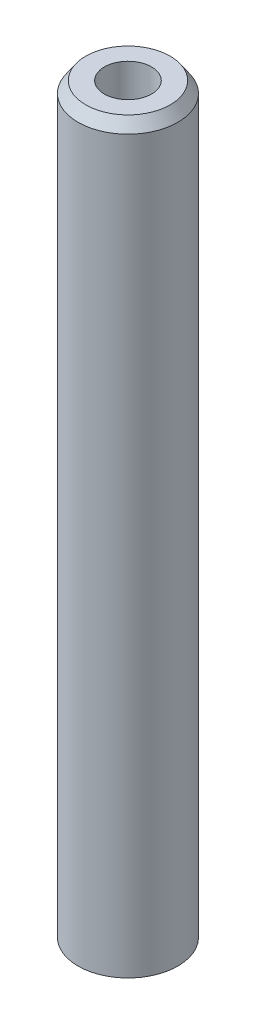
SolidWorks part; units mm, degrees
ref_plane "Front Plane" through (0, 0, 0) normal (0, 0, 1) x (1, 0, 0)
ref_plane "Top Plane" through (0, 0, 0) normal (0, 1, 0) x (1, 0, 0)
ref_plane "Right Plane" through (0, 0, 0) normal (1, 0, 0) x (0, 0, -1)
sketch "Sketch1" plane through (0, 0, 0) normal (0, 1, 0) x (1, 0, 0)
  circle A0 centre (0, 0) radius 10
  dimension "SHAFT_OD" = 20
extrude "Boss-Extrude1" add sketch "Sketch1" along normal blind 150.1847
sketch "Sketch2" plane through (0, 0, 0) normal (0, 1, 0) x (1, 0, 0)
  circle A0 centre (0, 0) radius 4.7216
  dimension "BORE_D" = 9.4432
extrude "Cut-Extrude1" cut sketch "Sketch2" along normal through all
chamfer "Chamfer1" distance 2.2546 angle 34.359 2 edges at (0, 150.1847, 10) (0, 0, 10) first distance on face at (0, 150.1847, 10) first distance on face at (0, 0, 4.7216)
